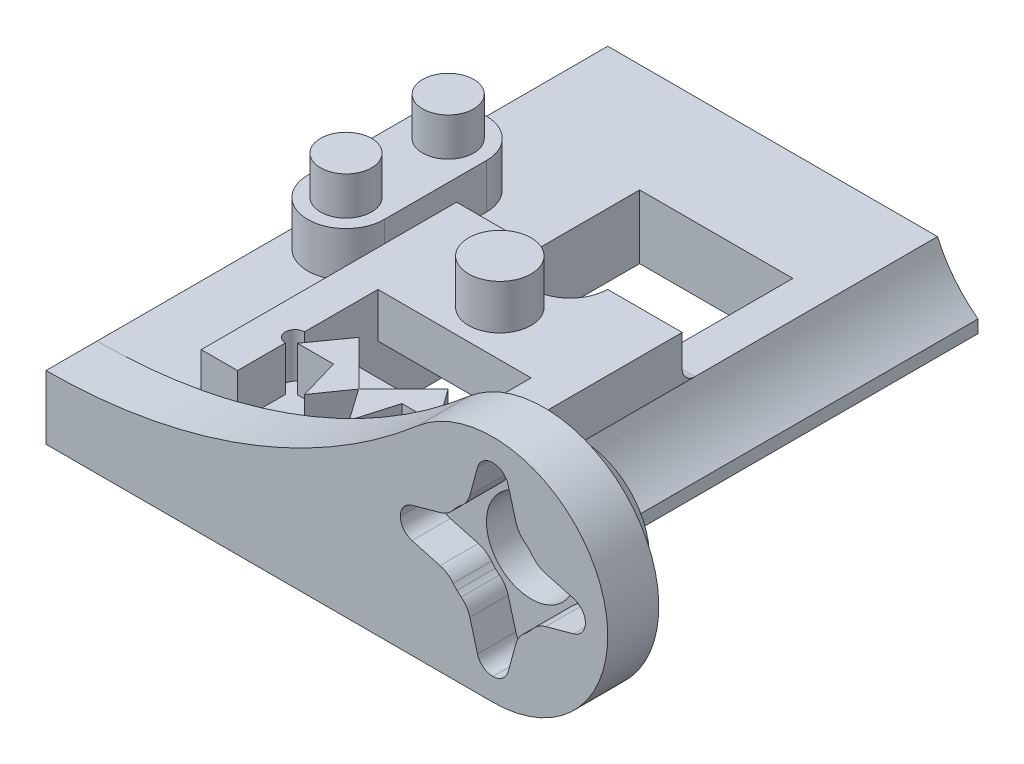
SolidWorks part; units mm, degrees
ref_plane "Front Plane" through (0, 0, 0) normal (0, 0, 1) x (1, 0, 0)
ref_plane "Top Plane" through (0, 0, 0) normal (0, 1, 0) x (1, 0, 0)
ref_plane "Right Plane" through (0, 0, 0) normal (1, 0, 0) x (0, 0, -1)
sketch "Sketch1" plane through (0, 0, 0) normal (0, 0, 1) x (1, 0, 0)
  line L0 (0, -9) -> (-35, -9)
  line L1 (-35, -9) -> (-35, -4)
  circle A0 centre (0, 0) radius 9
  arc A1 (-35, -4) -> (-5.8726, 6.82) centre (-35.0202, 40.6697) ccw
  dimension "D1" = 18
  dimension "D2" = 5
  dimension "D3" = 35
  dimension "D4" = 10.82
extrude "Boss-Extrude1" add sketch "Sketch1" along normal blind 4 contours A1 L1 L0 A0 | A0 region at (-18.5529, -4.8443, 0) region at (0, 0, 0)
sketch "Sketch2" plane through (0, 0, 0) normal (0, 0, -1) x (-1, 0, 0)
  circle A0 centre (0, 0) radius 7
  dimension "D1" = 14
extrude "Boss-Extrude2" add sketch "Sketch2" along normal blind 3 draft 30
sketch "Sketch4" plane through (0, 0, 4) normal (0, 0, 1) x (1, 0, 0)
  line L0 (0, 7.25) -> (0, -7.25) construction
  line L1 (1.2, -6.33) -> (1.8, -4.1378)
  line L2 (0, 0) -> (17.5555, 0) construction
  line L3 (0, 0) -> (8.976, -8.976) construction
  line L4 (6.33, -1.2) -> (4.1378, -1.8)
  line L5 (6.33, 1.2) -> (4.1378, 1.8)
  line L6 (1.2, 6.33) -> (1.8, 4.1378)
  line L7 (-1.2, 6.33) -> (-1.8, 4.1378)
  line L8 (-6.33, 1.2) -> (-4.1378, 1.8)
  line L9 (-6.33, -1.2) -> (-4.1378, -1.8)
  line L10 (-1.2, -6.33) -> (-1.8, -4.1378)
  arc A0 (0, -7.25) -> (1.2, -6.33) centre (-0.0057, -6) ccw
  arc A1 (1.8, -4.1378) -> (2.48, -3.1078) centre (3.7276, -4.671) cw
  arc A2 (2.48, -3.1078) -> (2.8116, -2.8116) centre (-0.0153, 0.0185) ccw
  arc A3 (3.1078, -2.48) -> (2.8116, -2.8116) centre (-0.0185, 0.0153) cw
  arc A4 (4.1378, -1.8) -> (3.1078, -2.48) centre (4.671, -3.7276) ccw
  arc A5 (7.25, 0) -> (6.33, 1.2) centre (6, -0.0057) ccw
  arc A6 (7.25, 0) -> (6.33, -1.2) centre (6, 0.0057) cw
  arc A7 (4.1378, 1.8) -> (3.1078, 2.48) centre (4.671, 3.7276) cw
  arc A8 (3.1078, 2.48) -> (2.8116, 2.8116) centre (-0.0185, -0.0153) ccw
  arc A9 (2.48, 3.1078) -> (2.8116, 2.8116) centre (-0.0153, -0.0185) cw
  arc A10 (1.8, 4.1378) -> (2.48, 3.1078) centre (3.7276, 4.671) ccw
  arc A11 (0, 7.25) -> (1.2, 6.33) centre (-0.0057, 6) cw
  arc A12 (0, 7.25) -> (-1.2, 6.33) centre (0.0057, 6) ccw
  arc A13 (-1.8, 4.1378) -> (-2.48, 3.1078) centre (-3.7276, 4.671) cw
  arc A14 (-2.48, 3.1078) -> (-2.8116, 2.8116) centre (0.0153, -0.0185) ccw
  arc A15 (-3.1078, 2.48) -> (-2.8116, 2.8116) centre (0.0185, -0.0153) cw
  arc A16 (-4.1378, 1.8) -> (-3.1078, 2.48) centre (-4.671, 3.7276) ccw
  arc A17 (-7.25, 0) -> (-6.33, -1.2) centre (-6, 0.0057) ccw
  arc A18 (-7.25, 0) -> (-6.33, 1.2) centre (-6, -0.0057) cw
  arc A19 (-4.1378, -1.8) -> (-3.1078, -2.48) centre (-4.671, -3.7276) cw
  arc A20 (-3.1078, -2.48) -> (-2.8116, -2.8116) centre (0.0185, 0.0153) ccw
  arc A21 (-2.48, -3.1078) -> (-2.8116, -2.8116) centre (0.0153, 0.0185) cw
  arc A22 (-1.8, -4.1378) -> (-2.48, -3.1078) centre (-3.7276, -4.671) ccw
  arc A23 (0, -7.25) -> (-1.2, -6.33) centre (0.0057, -6) cw
  point P5 (0, 0)
  dimension "D4" = 1.25
  dimension "D7" = 2
  dimension "D11" = 4
  dimension "D1" = 14.5
  dimension "D2" = 0.92
  dimension "D3" = 1.2
  dimension "D5" = 0.6
  dimension "D6" = 1.03
  dimension "D8" = 0.68
  dimension "D12" = 45
extrude "Cut-Extrude1" cut sketch "Sketch4" against normal blind 3
sketch "Sketch5" plane through (0, 0, 0) normal (0, 0, -1) x (-1, 0, 0)
  line L0 (35, -9) -> (35, -4)
  line L1 (35, -4) -> (9.17, -4)
  line L2 (35, -9) -> (6, -9)
  line L3 (0, -9) -> (35, -9) construction
  line L4 (6, -9) -> (6, -8)
  arc A0 (6, -8) -> (9.17, -4) centre (0.0072, 0.0054) ccw
  dimension "D4" = 10
  dimension "D1" = 29
  dimension "D2" = 25.83
  dimension "D3" = 1
extrude "Boss-Extrude3" add sketch "Sketch5" along normal blind 40
sketch "Sketch6" plane through (0, -4, 0) normal (0, 1, 0) x (1, 0, 0)
  line L0 (-9.17, 40) -> (-9.17, 0) construction
  line L1 (-24, 31.5) -> (-12, 31.5)
  line L2 (-24, 31.5) -> (-24, 8.5)
  line L3 (-24, 8.5) -> (-12, 8.5)
  line L4 (-12, 31.5) -> (-12, 8.5)
  line L5 (-35, 40) -> (-9.17, 40) construction
  dimension "D1" = 12
  dimension "D2" = 23
  dimension "D3" = 2.83
  dimension "D4" = 8.5
extrude "Cut-Extrude2" cut sketch "Sketch6" against normal through all
sketch "Sketch7" plane through (0, -4, 0) normal (0, 1, 0) x (1, 0, 0)
  line L0 (-12, 20) -> (-43.3143, 20) construction
  line L1 (-12, 8.5) -> (-12, 31.5) construction
  line L2 (-31.5, 24) -> (-31.5, 16) construction
  line L3 (-28.5, 24) -> (-28.5, 16)
  line L4 (-34.5, 24) -> (-34.5, 16)
  line L5 (-35, 40) -> (-35, 0) construction
  arc A0 (-28.5, 24) -> (-34.5, 24) centre (-31.5, 24) ccw
  arc A1 (-34.5, 16) -> (-28.5, 16) centre (-31.5, 16) ccw
  point P6 (-31.5, 20)
  dimension "D1" = 3
  dimension "D2" = 0.5
  dimension "D3" = 8
extrude "Boss-Extrude4" add sketch "Sketch7" along normal blind 3.5
sketch "Sketch8" plane through (0, -0.5, 0) normal (0, 1, 0) x (1, 0, 0)
  line L0 (-34.5, 20) -> (-28.5, 20) construction
  line L1 (-34.5, 24) -> (-34.5, 16) construction
  line L2 (-28.5, 16) -> (-28.5, 24) construction
  line L3 (-28.5, 20) -> (-31.5, 20) construction
  line L4 (-31.5, 20) -> (-31.5, 24) construction
  circle A0 centre (-31.5, 24) radius 2
  circle A1 centre (-31.5, 16) radius 2
  dimension "D2" = 4
  dimension "D1" = 4
extrude "Boss-Extrude5" add sketch "Sketch8" along normal blind 3
sketch "Sketch9" plane through (0, 0, -3) normal (0, 0, -1) x (-1, 0, 0)
  circle A0 centre (0, 0) radius 3.5
  dimension "D1" = 7
extrude "Cut-Extrude3" cut sketch "Sketch9" against normal through all
sketch "Sketch10" plane through (0, -4, 0) normal (0, 1, 0) x (1, 0, 0)
  line L0 (-26.84, 0) -> (-26.84, 20)
  line L1 (-5.8726, 0) -> (-35, 0) construction
  line L3 (-26.84, 20) -> (-21.01, 20)
  line L4 (-15.0109, 20) -> (-9.17, 20)
  line L5 (-9.17, 40) -> (-9.17, 0) construction
  line L6 (-9.17, 20) -> (-9.17, 0)
  line L7 (-24, 0) -> (-24, 3.75)
  line L8 (-12, 0) -> (-12, 3.75)
  line L9 (-35, 0) -> (-9.17, 0) construction
  line L12 (-24, 5.25) -> (-24, 11)
  line L13 (-24, 31.5) -> (-24, 8.5) construction
  line L14 (-24, 11) -> (-12, 11)
  line L15 (-18, 8.5) -> (-18, 14.8282) construction
  line L16 (-24, 8.5) -> (-12, 8.5) construction
  line L17 (-12, 5.25) -> (-12, 11)
  line L20 (-26.84, 0) -> (-24, 0)
  line L21 (-12, 0) -> (-9.17, 0)
  line L22 (-12, 8.5) -> (-12, 31.5) construction
  arc A0 (-21.01, 20) -> (-15.0109, 20) centre (-18.0105, 20.0527) ccw
  arc A1 (-24, 5.25) -> (-24, 3.75) centre (-24, 4.5) ccw
  arc A2 (-12, 5.25) -> (-12, 3.75) centre (-12, 4.5) cw
  point P31 (-18, 11)
  point P44 (-25.42, 0)
  dimension "D4" = 5.83
  dimension "D7" = 0.75
  dimension "D3" = 3
  dimension "D1" = 20
  dimension "D2" = 17.67
  dimension "D5" = 3.75
  dimension "D6" = 11
extrude "Boss-Extrude6" add sketch "Sketch10" along normal blind 3.5
sketch "Sketch11" plane through (0, -0.5, 0) normal (0, 1, 0) x (1, 0, 0)
  line L0 (-18.0105, 17.0527) -> (-18, 11) construction
  line L1 (-24, 11) -> (-12, 11) construction
  arc A0 (-21.01, 20) -> (-15.0109, 20) centre (-18.0105, 20.0527) ccw construction
  circle A1 centre (-18.0061, 14.5527) radius 2.45
  dimension "D1" = 4.9
  dimension "D2" = 2.5
extrude "Boss-Extrude7" add sketch "Sketch11" along normal blind 3.5
sketch "Sketch12" plane through (0, -4, 0) normal (0, 1, 0) x (1, 0, 0)
  line L0 (-26.84, 4.2) -> (-9.17, 4.2) construction
  line L1 (-26.84, 20) -> (-26.84, 0) construction
  line L2 (-9.17, 0) -> (-9.17, 20) construction
  line L3 (-26.84, 0) -> (-24, 0) construction
  line L4 (-18, 11) -> (-18, 0) construction
  line L5 (-24, 11) -> (-12, 11) construction
  line L6 (-24, 0) -> (-12, 0) construction
  line L7 (-20.68, 4.2) -> (-23.5, 4.2)
  line L8 (-23.5, 4.2) -> (-21.5, 7)
  line L9 (-20.68, 4.2) -> (-19.75, 1)
  line L10 (-19.75, 1) -> (-18.03, 3.45)
  line L11 (-18.03, 3.45) -> (-17.97, 3.45)
  line L12 (-21.5, 7) -> (-18.05, 3.55)
  line L13 (-18.05, 3.55) -> (-17.95, 3.55)
  line L14 (-14.5, 7) -> (-17.95, 3.55)
  line L15 (-16.25, 1) -> (-17.97, 3.45)
  line L16 (-15.32, 4.2) -> (-16.25, 1)
  line L17 (-12.5, 4.2) -> (-14.5, 7)
  line L18 (-15.32, 4.2) -> (-12.5, 4.2)
  point P23 (-18, 3.55)
  point P25 (-18, 3.45)
  dimension "D1" = 4.2
  dimension "D2" = 2.82
  dimension "D3" = 2
  dimension "D4" = 3.5
  dimension "D5" = 0.93
  dimension "D6" = 1.72
  dimension "D7" = 0.1
  dimension "D8" = 0.05
  dimension "D9" = 3.45
  dimension "D10" = 3.2
  dimension "D11" = 2.8
extrude "Boss-Extrude8" add sketch "Sketch12" along normal blind 3.5
fillet "Fillet3" radius 1 3 edges at (-26.84, -4, -10) (-25.42, -4, -20) (-10.585, -4, -20)
